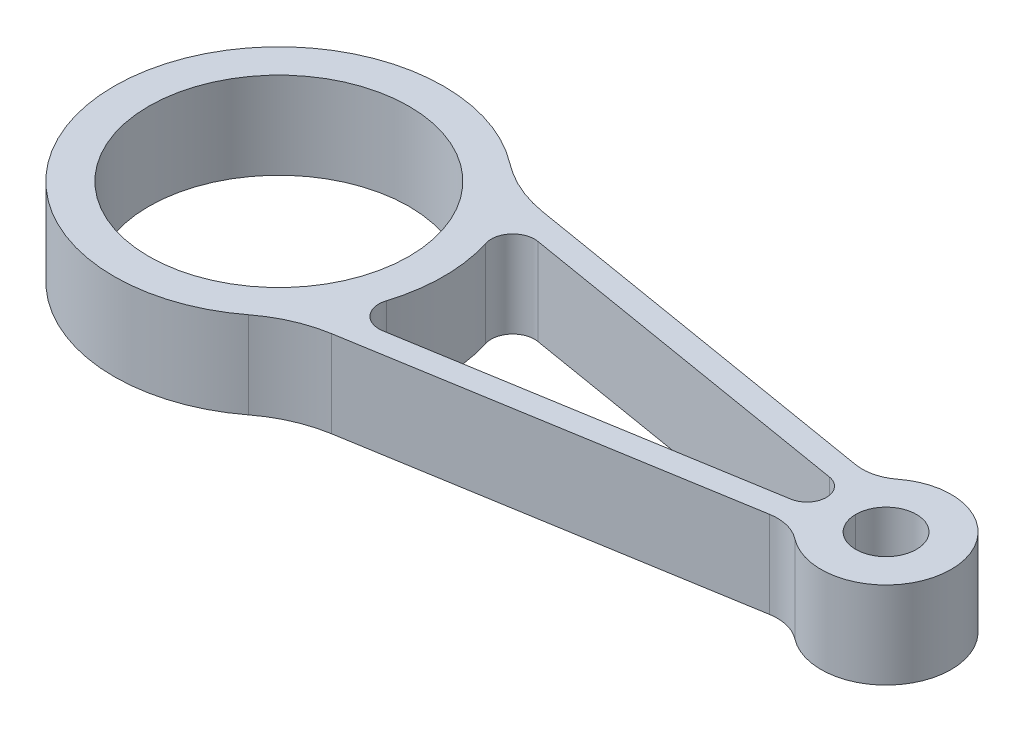
SolidWorks part; units mm, degrees
material "Plain Carbon Steel"
ref_plane "Front Plane" through (0, 0, 0) normal (0, 0, 1) x (1, 0, 0)
ref_plane "Top Plane" through (0, 0, 0) normal (0, 1, 0) x (1, 0, 0)
ref_plane "Right Plane" through (0, 0, 0) normal (1, 0, 0) x (0, 0, -1)
sketch "Sketch1" plane through (0, 0, 0) normal (0, 1, 0) x (1, 0, 0)
  line L0 (-70.1354, 0) -> (160.5153, 0) construction
  line L1 (154.2362, 4.7254) -> (162.3118, 3.3804)
  line L2 (161.8433, -3.4585) -> (154.2362, -4.7254)
  line L3 (27.9355, 25.7606) -> (128.0638, 9.0844)
  line L4 (128.0638, -9.0844) -> (27.9355, -25.7606)
  circle A0 centre (0, 0) radius 30
  circle A1 centre (140, 0) radius 7
  arc A2 (27.9355, 25.7606) -> (27.9355, -25.7606) centre (0, 0) ccw
  arc A3 (128.0638, -9.0844) -> (128.0638, 9.0844) centre (140, 0) ccw
  dimension "D2" = 60
  dimension "D3" = 76
  dimension "D4" = 14
  dimension "D5" = 30
  dimension "D1" = 140
extrude "Boss-Extrude1" add sketch "Sketch1" along normal mid plane 20 contours L0 A2 L4 A3 A1 A0 | A2 L0 A0 A1 A3 L3 region at (57.0238, 0, -13.1191) region at (57.0238, 0, 13.1191)
fillet "Fillet1" radius 30 2 edges at (27.9355, 0, 25.7606) (27.9355, 0, -25.7606)
fillet "Fillet2" radius 10 2 edges at (128.0638, 0, 9.0844) (128.0638, 0, -9.0844)
sketch "Sketch2" plane through (0, 10, 0) normal (0, 1, 0) x (1, 0, 0)
  line L0 (0, 0) -> (172.9584, 0) construction
  line L1 (41.8286, 17.871) -> (122.4784, 4.4389)
  line L2 (122.4784, -4.4389) -> (41.8286, -17.871)
  line L3 (36.4938, 24.3352) -> (123.0688, 9.9163) construction
  arc A0 (36.2389, 11.4344) -> (36.2389, -11.4344) centre (0, 0) cw
  arc A1 (36.2389, 11.4344) -> (41.8286, 17.871) centre (41.0071, 12.9389) cw
  arc A2 (36.2389, -11.4344) -> (41.8286, -17.871) centre (41.0071, -12.9389) ccw
  arc A3 (122.4784, -4.4389) -> (122.4784, 4.4389) centre (121.7391, 0) ccw
  circle A4 centre (0, 0) radius 30 construction
  point P16 (0, 0)
  point P17 (0, 0)
  point P18 (126.5503, 3.7607)
  point P19 (39.9616, 13.2709)
  point P20 (40.7826, -13.6302)
  point P21 (122.8152, 0)
  point P22 (43.9211, -17.5225)
  point P23 (40.7826, -13.6302)
  point P24 (36.1028, -11.8569)
  point P25 (43.919, 17.5228)
  dimension "D1" = 5
  dimension "D2" = 4.5
  dimension "D4" = 8
  dimension "D3" = 5.5
extrude "Cut-Extrude1" cut sketch "Sketch2" against normal through all
split line "Split Line1"
